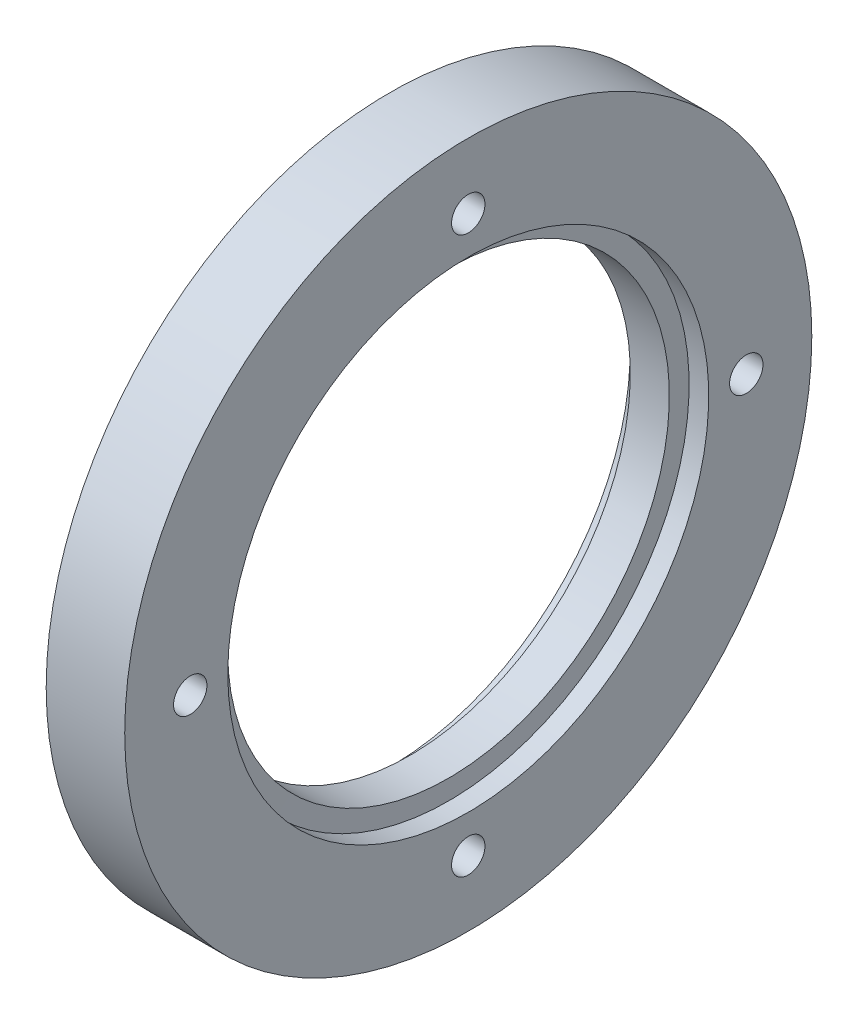
SolidWorks part; units mm, degrees
ref_plane "Front Plane" through (0, 0, 0) normal (0, 0, 1) x (1, 0, 0)
ref_plane "Top Plane" through (0, 0, 0) normal (0, 1, 0) x (1, 0, 0)
ref_plane "Right Plane" through (0, 0, 0) normal (1, 0, 0) x (0, 0, -1)
sketch "Sketch1" plane through (0, 0, 0) normal (0, 0, 1) x (1, 0, 0)
  line L0 (-801.9206, 0) -> (36107.5283, 0) construction
  line L10 (17.6402, 24.5) -> (17.6402, 35)
  line L12 (17.6402, 35) -> (9.6402, 35)
  line L16 (17.6402, 24.5) -> (15.6402, 24.5)
  line L17 (15.6402, 24.5) -> (15.6285, 22.5)
  line L18 (9.6402, 35) -> (9.6402, 24.5)
  line L22 (13.6285, 22.5) -> (15.6285, 22.5)
  line L28 (9.6402, 24.5) -> (11.6402, 24.5)
  line L29 (11.6402, 24.5) -> (11.6519, 22.5)
  line L30 (11.6519, 22.5) -> (13.6285, 22.5)
  point P1 (9.64, 22.5)
  dimension "D1" = 8
  dimension "D5" = 35
  dimension "D3" = 2
  dimension "D8" = 24.5
  dimension "D9" = 2
  dimension "D10" = 2
revolve "Revolve17" add sketch "Sketch1" angle 360 about L0
sketch "Sketch4" plane through (9.6402, 0, 0) normal (-1, 0, 0) x (0, 0, 1)
  circle A0 centre (0, 0) radius 28.325 construction
  point P3 (0, 28.325)
  point P7 (28.325, 0)
  point P12 (-28.325, 0)
  point P13 (0, -28.325)
  dimension "D1" = 56.65
hole_wizard "M3 Clearance Hole1" positions "Sketch4" profile "Sketch5" hole size "M3" standard "ISO"
sketch "Sketch5" plane through (9.6402, -28.325, 0) normal (0, 1, 0) x (0, 0, 1)
  line L0 (0, 0) -> (0, 9.0215)
  line L1 (0, 9.0215) -> (1.7, 8)
  line L2 (1.7, 8) -> (1.7, 0)
  line L5 (1.7, 0) -> (0, 0)
  line L10 (0, 9.0215) -> (-1.7, 8) construction
  line L11 (0, -6.35) -> (0, 107.95) construction
  dimension "Hole Dia." = 3.4
  dimension "Hole Depth" = 8
  dimension "Drill Angle" = 118
